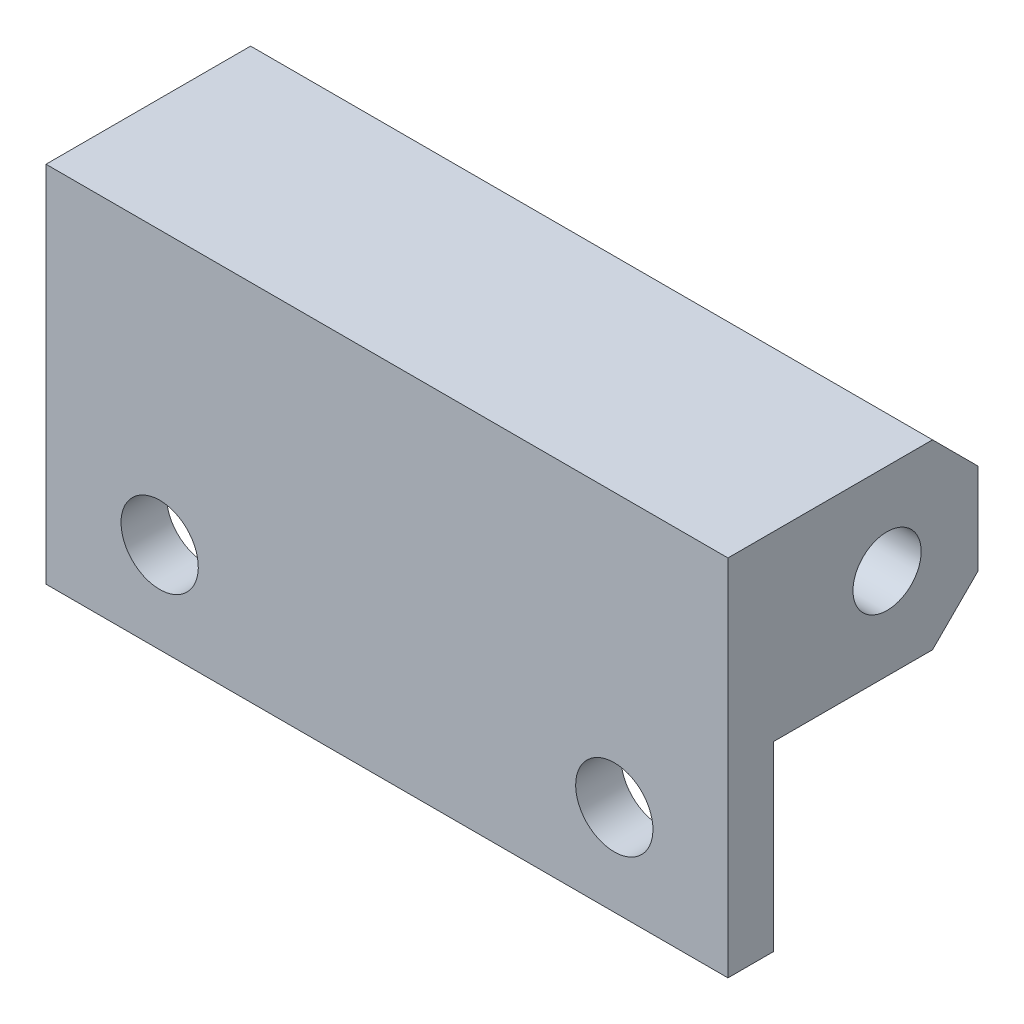
SolidWorks part; units mm, degrees
material "6061 Alloy"
ref_plane "Front Plane" through (0, 0, 0) normal (0, 0, 1) x (1, 0, 0)
ref_plane "Top Plane" through (0, 0, 0) normal (0, 1, 0) x (1, 0, 0)
ref_plane "Right Plane" through (0, 0, 0) normal (1, 0, 0) x (0, 0, -1)
sketch "Sketch1" plane through (0, 0, 0) normal (1, 0, 0) x (0, 0, -1)
  line L0 (-7, 4) -> (2, 4)
  line L1 (2, -4) -> (-5, -4)
  line L2 (-5, -4) -> (-5, -12)
  line L3 (-5, -12) -> (-7, -12)
  line L4 (-7, -12) -> (-7, 4)
  line L5 (2, -4) -> (4, -2)
  line L6 (4, -2) -> (4, 2)
  line L7 (4, 2) -> (2, 4)
  point P9 (4, 0)
  dimension "D1" = 8
  dimension "D2" = 5
  dimension "D3" = 2
  dimension "D4" = 8
  dimension "D5" = 4
  dimension "D6" = 45
  dimension "D7" = 4
extrude "Boss-Extrude1" add sketch "Sketch1" along normal mid plane 30 contours L1 L2 L3 L4 L0 L7 L6 L5
hole_wizard "M3 Clearance Hole1" positions "Sketch2" profile "Sketch3" hole size "M3" standard "ANSI Metric" end condition through all
sketch "Sketch2" plane through (0, 0, 5) normal (0, 0, -1) x (-1, 0, 0)
  line L1 (-15, -4) -> (-15, -12) construction
  line L2 (15, -4) -> (15, -12) construction
  line L3 (-15, -4) -> (15, -4) construction
  point P0 (-10, -8)
  point P2 (10, -8)
  dimension "D1" = 5
  dimension "D2" = 5
  dimension "D3" = 4
sketch "Sketch3" plane through (10, -8, 5) normal (1, 0, 0) x (0, 1, 0)
  line L0 (0, 0) -> (0, 2)
  line L1 (0, 2) -> (1.7, 2)
  line L2 (1.7, 2) -> (1.7, 0)
  line L5 (1.7, 0) -> (0, 0)
  line L11 (0, -6.35) -> (0, 107.95) construction
  dimension "Thru Hole Dia." = 3.4
  dimension "Thru Hole Depth" = 2
sketch "Sketch4" plane through (15, 0, 0) normal (1, 0, 0) x (0, 0, -1)
  circle A0 centre (0, 0) radius 1.5
  dimension "D1" = 3
extrude "Cut-Extrude1" cut sketch "Sketch4" against normal through all and the other way through all
